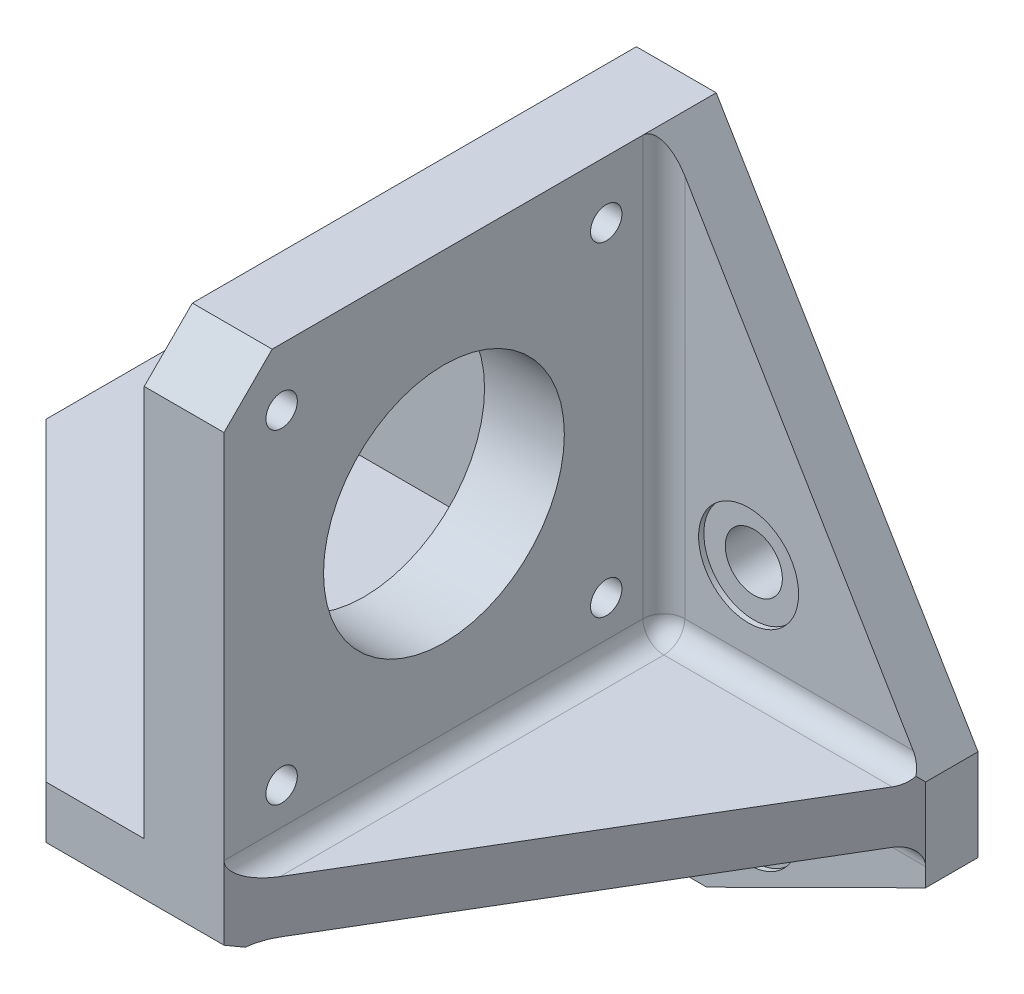
SolidWorks part; units mm, degrees
ref_plane "Front Plane" through (0, 0, 0) normal (0, 0, 1) x (1, 0, 0)
ref_plane "Top Plane" through (0, 0, 0) normal (0, 1, 0) x (1, 0, 0)
ref_plane "Right Plane" through (0, 0, 0) normal (1, 0, 0) x (0, 0, -1)
sketch "Sketch1" plane through (0, 0, 0) normal (0, 0, 1) x (1, 0, 0)
  line L1 (-23.5, -20) -> (23.5, -20)
  line L2 (-23.5, -20) -> (-23.5, 20)
  line L3 (-23.5, 20) -> (23.5, 20)
  line L4 (23.5, -20) -> (23.5, 20)
  line L5 (-23.5, -20) -> (23.5, 20) construction
  line L6 (-23.5, 20) -> (23.5, -20) construction
  point P0 (0, 0)
  dimension "D1" = 47
  dimension "D2" = 40
extrude "Boss-Extrude1" add sketch "Sketch1" along normal blind 5
sketch "Sketch2" plane through (0, 0, 5) normal (0, 0, 1) x (1, 0, 0)
  line L1 (23.5, 20) -> (15.88, 20)
  line L2 (23.5, 20) -> (23.5, -0.8469)
  line L3 (23.5, -0.8469) -> (15.88, -0.8469)
  line L4 (15.88, 20) -> (15.88, -0.8469)
  dimension "D1" = 7.62
  dimension "D2" = 20.8469
extrude "Boss-Extrude2" add sketch "Sketch2" along normal blind 42
sketch "Sketch4" plane through (0, 0, 0) normal (0, 0, -1) x (-1, 0, 0)
  line L0 (-15.88, 20) -> (-15.88, -0.8469) construction
  line L1 (-23.5, 20) -> (-15.88, 20)
  line L2 (-23.5, 20) -> (-23.5, 41.15)
  line L3 (-23.5, 41.15) -> (-15.88, 41.15)
  line L4 (-15.88, 20) -> (-15.88, 41.15)
  dimension "D1" = 21.15
extrude "Boss-Extrude3" add sketch "Sketch4" against normal up to surface (47 mm away) up to face at (19.69, 9.5765, 47)
sketch "Sketch3" plane through (23.5, 0, 0) normal (1, 0, 0) x (0, 0, -1)
  line L0 (-47, -0.8469) -> (-5, -0.8469) construction
  line L2 (-41.5, 4.6531) -> (-10.5, 4.6531) construction
  line L3 (-41.5, 4.6531) -> (-41.5, 35.6531) construction
  line L4 (-41.5, 35.6531) -> (-10.5, 35.6531) construction
  line L5 (-10.5, 4.6531) -> (-10.5, 35.6531) construction
  line L6 (-41.5, 4.6531) -> (-10.5, 35.6531) construction
  line L7 (-41.5, 35.6531) -> (-10.5, 4.6531) construction
  circle A0 centre (-26, 20.1531) radius 11.5
  circle A1 centre (-41.5, 35.6531) radius 1.5
  circle A2 centre (-10.5, 35.6531) radius 1.5
  circle A3 centre (-10.5, 4.6531) radius 1.5
  circle A4 centre (-41.5, 4.6531) radius 1.5
  point P5 (-26, -0.8469)
  dimension "D1" = 23
  dimension "D5" = 3
  dimension "D2" = 21
  dimension "D3" = 31
  dimension "D4" = 31
extrude "Cut-Extrude1" cut sketch "Sketch3" against normal through all
sketch "Sketch5" plane through (0, 0, 5) normal (0, 0, 1) x (1, 0, 0)
  line L0 (-23.5, 20) -> (-23.5, -20) construction
  line L1 (23.5, -0.8469) -> (-23.5, -0.8469)
  line L2 (23.5, -0.8469) -> (23.5, -5.8469)
  line L3 (23.5, -5.8469) -> (-23.5, -5.8469)
  line L4 (-23.5, -0.8469) -> (-23.5, -5.8469)
  dimension "D1" = 5
extrude "Boss-Extrude4" add sketch "Sketch5" along normal up to surface (42 mm away) up to face at (19.69, 20.1515, 47)
sketch "Sketch9" plane through (0, -0.8469, 0) normal (0, 1, 0) x (1, 0, 0)
  line L0 (23.5, -47) -> (48.5, -5)
  line L1 (48.5, 0) -> (23.5, 0)
  line L2 (23.5, 0) -> (23.5, -47)
  line L3 (48.5, -5) -> (48.5, 0)
  line L4 (23.5, -5) -> (23.5, 0) construction
  dimension "D1" = 25
extrude "Boss-Extrude8" add sketch "Sketch9" against normal up to surface (5 mm away) up to face at (0, -5.8469, 26)
sketch "Sketch10" plane through (0, 0, 0) normal (0, 0, -1) x (-1, 0, 0)
  line L0 (-48.5, -0.8469) -> (-23.5, 41.15)
  line L1 (-23.5, 41.15) -> (-23.5, -0.8469)
  line L2 (-23.5, -0.8469) -> (-48.5, -0.8469)
extrude "Boss-Extrude9" add sketch "Sketch10" against normal up to surface (5 mm away) up to face at (-3.81, 9.5765, 5)
sketch "Sketch12" plane through (0, 0, 0) normal (0, 0, -1) x (-1, 0, 0)
  line L0 (-23.5, -20) -> (-23.5, -5.8469)
  line L1 (-23.5, -5.8469) -> (-48.5, -5.8469)
  line L3 (-23.5, -20) -> (-27.5969, -20)
  line L4 (-27.5969, -20) -> (-48.5, -9.6014)
  line L5 (-48.5, -5.8469) -> (-48.5, -9.6014)
extrude "Boss-Extrude11" add sketch "Sketch12" against normal up to surface (5 mm away) up to face at (0, -12.9235, 5)
sketch "Sketch13" plane through (23.5, 0, 0) normal (1, 0, 0) x (0, 0, -1)
  line L0 (-5, -20) -> (-5, -5.8469)
  line L1 (-5, -5.8469) -> (-47, -5.8469)
  line L2 (-47, -5.8469) -> (-5, -20)
extrude "Boss-Extrude12" add sketch "Sketch13" against normal up to surface (7.62 mm away) up to face at (15.88, 6.1531, 41.5)
sketch "Sketch17" plane through (0, -5.8469, 0) normal (0, -1, 0) x (1, 0, 0)
  line L0 (-23.5, 17) -> (6.5, 47)
  line L1 (-23.5, 47) -> (-23.5, 5) construction
  line L2 (15.88, 47) -> (-23.5, 47) construction
  line L3 (6.5, 47) -> (-23.5, 47)
  line L4 (-23.5, 47) -> (-23.5, 17)
  dimension "D1" = 30
  dimension "D2" = 30
extrude "Cut-Extrude5" cut sketch "Sketch17" against normal through all
sketch "Sketch18" plane through (0, 0, 5) normal (0, 0, 1) x (1, 0, 0)
  line L1 (15.88, 41.15) -> (15.88, -0.8469)
  line L2 (15.88, -0.8469) -> (-23.5, -0.8469)
  line L3 (-23.5, -0.8469) -> (-23.5, 41.15)
  line L4 (-23.5, 41.15) -> (15.88, 41.15)
extrude "Cut-Extrude7" cut sketch "Sketch18" against normal through all
sketch "Sketch22" plane through (23.5, 0, 0) normal (1, 0, 0) x (0, 0, -1)
  line L6 (-47, 41.15) -> (-47, 36.5538)
  line L7 (-47, -0.8469) -> (-47, 41.15) construction
  line L8 (-47, 36.5538) -> (-42.4038, 41.15)
  line L9 (-47, 41.15) -> (-5, 41.15) construction
  line L10 (-42.4038, 41.15) -> (-47, 41.15)
  dimension "D1" = 6.5
extrude "Cut-Extrude10" cut sketch "Sketch22" against normal through all
sketch "Sketch19" plane through (0, 0, 0) normal (0, 0, -1) x (-1, 0, 0)
  line L0 (-15.88, 41.15) -> (-15.88, -0.8469)
  line L1 (-15.88, -0.8469) -> (23.5, -0.8469)
  line L2 (23.5, -0.8469) -> (-15.88, 41.15)
extrude "Boss-Extrude13" add sketch "Sketch19" against normal up to surface (5 mm away) up to face at (-3.81, -12.9235, 5)
sketch "Sketch14" plane through (0, 0, 0) normal (0, 0, 1) x (1, 0, 0)
  circle A0 centre (31.5938, 8.6194) radius 2.725
  circle A1 centre (31.5938, -11.3806) radius 2.725
  circle A2 centre (1.6564, -11.3806) radius 2.725
  circle A3 centre (1.6564, -11.3806) radius 4.775 construction
  circle A4 centre (31.5938, 8.6194) radius 4.775 construction
  circle A5 centre (31.5938, -11.3806) radius 4.775 construction
  dimension "D1" = 5.45
  dimension "D2" = 20
extrude "Holes" cut sketch "Sketch14" along normal through all
sketch "Sketch21" plane through (0, 0, 5) normal (0, 0, 1) x (1, 0, 0)
  circle A0 centre (31.5938, 8.6194) radius 4.775 construction
  circle A1 centre (31.5938, -11.3806) radius 4.775 construction
  circle A2 centre (1.6564, -11.3806) radius 4.775 construction
  circle A3 centre (31.5938, 8.6194) radius 4.775
  circle A4 centre (31.5938, -11.3806) radius 4.775
  circle A5 centre (1.6564, -11.3806) radius 4.775
extrude "Counter Sink" cut sketch "Sketch21" against normal blind 0.5
sketch "Sketch20" plane through (0, 0, 5) normal (0, 0, 1) x (1, 0, 0)
  line L0 (-23.5, -5.8469) -> (3.2535, -20)
  line L1 (-23.5, -20) -> (15.88, -20) construction
  line L2 (3.2535, -20) -> (-23.5, -20)
  line L3 (-23.5, -20) -> (-23.5, -5.8469)
extrude "Cut-Extrude8" cut sketch "Sketch20" against normal through all
fillet "Fillet1" radius 2 9 edges at (15.88, -5.8469, 26) (15.88, -12.9235, 5) (-3.81, -5.8469, 5) (36, -5.8469, 5) (23.5, -12.9235, 5) (23.5, -5.8469, 26) (36, -0.8469, 5) (23.5, -0.8469, 26) (23.5, 20.1515, 5)
